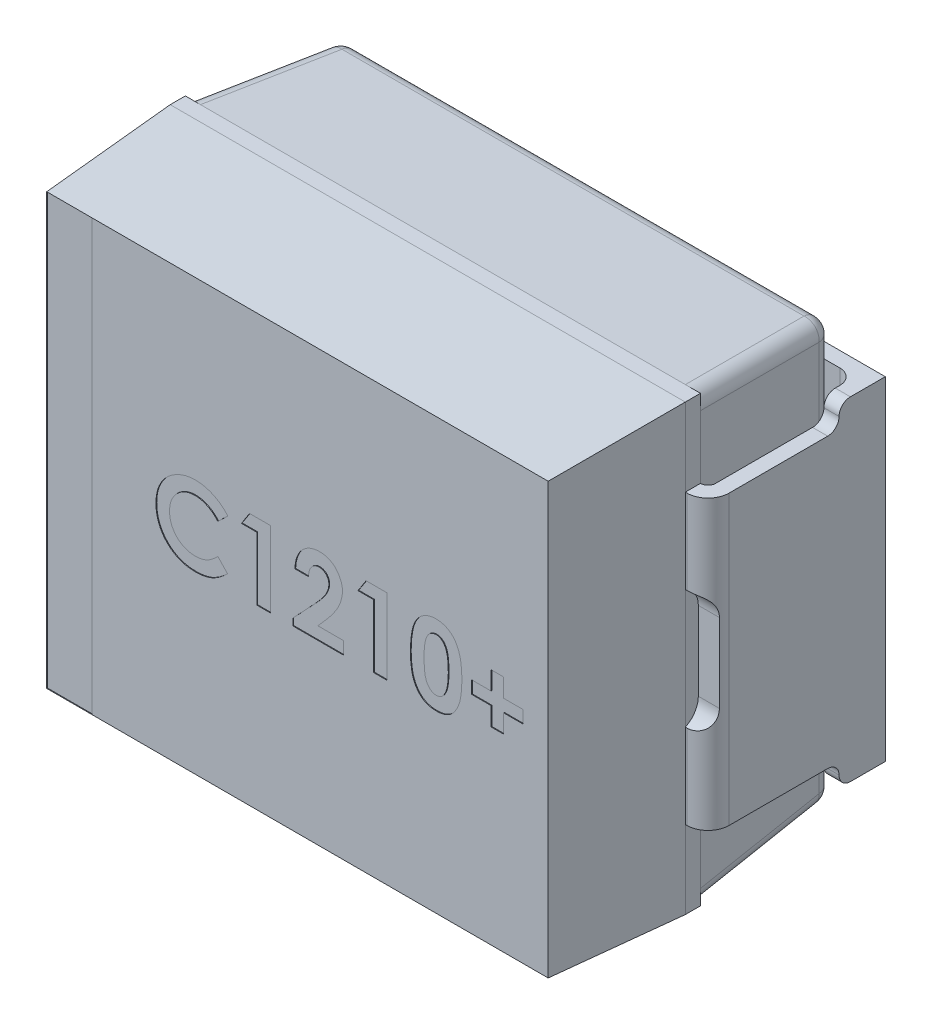
SolidWorks part; units mm, degrees
ref_plane "Front Plane" through (0, 0, 0) normal (0, 0, 1) x (1, 0, 0)
ref_plane "Top Plane" through (0, 0, 0) normal (0, 1, 0) x (1, 0, 0)
ref_plane "Right Plane" through (0, 0, 0) normal (1, 0, 0) x (0, 0, -1)
sketch "Sketch1" plane through (0, 0, 0) normal (0, 0, 1) x (1, 0, 0)
  line L1 (-1.7, -1.465) -> (-1.7, 1.465)
  line L2 (-1.7, -1.465) -> (1.7, -1.465)
  line L3 (1.7, -1.465) -> (1.7, 1.465)
  line L4 (-1.7, 1.465) -> (1.7, 1.465)
  dimension "D1" = 3.4
  dimension "D2" = 2.93
  dimension "D3" = 1.465
  dimension "D4" = 1.7
extrude "Boss-Extrude1" add sketch "Sketch1" along normal blind 0.95 from offset 0.12
ref_plane "Plane1" through (0, 0, 1.07) normal (0, 0, 1) x (1, 0, 0)
ref_plane "Plane2" through (0, 0, 1.17) normal (0, 0, 1) x (1, 0, 0)
sketch "Sketch2" plane through (0, 0, 1.07) normal (0, 0, 1) x (1, 0, 0)
  line L1 (-1.7, -1.465) -> (-1.7, 1.465)
  line L2 (-1.7, -1.465) -> (1.7, -1.465)
  line L3 (1.7, -1.465) -> (1.7, 1.465)
  line L4 (-1.7, 1.465) -> (1.7, 1.465)
  dimension "D1" = 1.7
  dimension "D2" = 2.93
  dimension "D3" = 1.465
  dimension "D4" = 3.4
sketch "Sketch3" plane through (0, 0, 1.17) normal (0, 0, 1) x (1, 0, 0)
  line L1 (-1.7, -1.465) -> (-1.7, 1.465)
  line L2 (-1.7, -1.465) -> (1.7, -1.465)
  line L3 (1.7, -1.465) -> (1.7, 1.465)
  line L4 (-1.7, 1.465) -> (1.7, 1.465)
  dimension "D1" = 1.465
  dimension "D2" = 2.93
  dimension "D3" = 1.7
  dimension "D4" = 3.4
chamfer "Chamfer3" distance 0.95 angle 5 4 edges at (0, -1.465, 0.12) (1.7, 0, 0.12) (0, 1.465, 0.12) (-1.7, 0, 0.12) first distance on face at (0, -1.465, 0.595) first distance on face at (1.7, 0, 0.595) first distance on face at (0, 1.465, 0.595) first distance on face at (-1.7, 0, 0.595)
fillet "Fillet4" radius 0.1 8 edges at (-1.6584, -1.4234, 0.595) (1.6584, -1.4234, 0.595) (1.6584, 1.4234, 0.595) (-1.6584, 1.4234, 0.595) (1.6169, 0, 0.12) (0, -1.3819, 0.12) (-1.6169, 0, 0.12) (0, 1.3819, 0.12)
extrude "Boss-Extrude2" add sketch "Sketch2" along normal blind 0.1
extrude "Boss-Extrude3" add sketch "Sketch3" along normal blind 0.86 draft 3
sketch "Sketch4" plane through (0, 0, 0) normal (0, 0, 1) x (1, 0, 0)
  line L1 (-0.7, -1.25) -> (-0.7, 1.25)
  line L2 (-0.7, -1.25) -> (0.7, -1.25)
  line L3 (0.7, -1.25) -> (0.7, 1.25)
  line L4 (-0.7, 1.25) -> (0.7, 1.25)
  dimension "D1" = 0.7
  dimension "D2" = 2.5
  dimension "D3" = 1.4
  dimension "D4" = 1.25
extrude "Boss-Extrude4" add sketch "Sketch4" along normal blind 0.1 from offset 0.02
fillet "Fillet5" radius 0.1 4 edges at (0, -1.25, 0.02) (0.7, 0, 0.02) (0, 1.25, 0.02) (-0.7, 0, 0.02)
sketch "Sketch6" plane through (0, 0, 0) normal (0, 1, 0) x (1, 0, 0)
  line L0 (-1.7, -1.17) -> (-1.7, -1.07)
  line L1 (-1.6116, -1.17) -> (1.6116, -1.17) construction
  line L2 (-1.6549, -2.03) -> (-1.7, -1.17) construction
  line L3 (-1.6116, -1.07) -> (1.6116, -1.07) construction
  line L4 (-1.7, -1.17) -> (-1.7, -1.07) construction
  line L5 (-1.7, -1.07) -> (-1.701, -1.07)
  line L6 (-1.75, -1.021) -> (-1.75, -0.2)
  line L7 (-1.65, -0.1) -> (-1.15, -0.1)
  line L8 (0, -0.02) -> (0, -2.03) construction
  line L9 (-1.15, -0.1) -> (-1.15, 0)
  line L10 (-1.15, 0) -> (-1.85, 0)
  line L11 (-1.85, 0) -> (-1.85, -1.03)
  line L12 (-1.71, -1.17) -> (-1.7, -1.17)
  line L13 (-0.6, -0.02) -> (0.6, -0.02) construction
  line L14 (1.6549, -2.03) -> (-1.6549, -2.03) construction
  line L15 (1.71, -1.17) -> (1.7, -1.17)
  line L16 (1.85, 0) -> (1.85, -1.03)
  line L17 (1.15, 0) -> (1.85, 0)
  line L18 (1.15, -0.1) -> (1.15, 0)
  line L19 (1.65, -0.1) -> (1.15, -0.1)
  line L20 (1.75, -1.021) -> (1.75, -0.2)
  line L21 (1.7, -1.07) -> (1.701, -1.07)
  line L22 (1.7, -1.17) -> (1.7, -1.07)
  arc A0 (-1.85, -1.03) -> (-1.71, -1.17) centre (-1.71, -1.03) ccw
  arc A1 (-1.701, -1.07) -> (-1.75, -1.021) centre (-1.701, -1.021) cw
  arc A2 (-1.75, -0.2) -> (-1.65, -0.1) centre (-1.65, -0.2) cw
  arc A3 (1.75, -0.2) -> (1.65, -0.1) centre (1.65, -0.2) ccw
  arc A4 (1.701, -1.07) -> (1.75, -1.021) centre (1.701, -1.021) ccw
  arc A5 (1.85, -1.03) -> (1.71, -1.17) centre (1.71, -1.03) cw
  point P15 (-1.85, -1.17)
  point P21 (-1.75, -1.07)
  point P24 (-1.75, -0.1)
  point P45 (1.75, -0.1)
  point P46 (1.75, -1.07)
  point P47 (1.85, -1.17)
  dimension "D6" = 0.14
  dimension "D7" = 0.049
  dimension "D8" = 0.1
  dimension "D1" = 0.97
  dimension "D2" = 0.15
  dimension "D3" = 0.1
  dimension "D4" = 0.1
  dimension "D5" = 0.7
extrude "Boss-Extrude5" add sketch "Sketch6" along normal mid plane 2.2
ref_plane "Plane3" through (-1.85, 0, 0) normal (-1, 0, 0) x (0, 0, 1)
sketch "Sketch7" plane through (-1.85, 0, 0) normal (-1, 0, 0) x (0, 0, 1)
  line L0 (0, 0) -> (2.03, 0) construction
  line L1 (2.03, 1.4199) -> (2.03, -1.4199) construction
  line L2 (1.17, 1.1) -> (1.17, -1.1) construction
  line L4 (1.17, 0.475) -> (0.559, 0.475)
  line L5 (1.17, 0.475) -> (1.17, -0.475)
  line L6 (1.17, -0.475) -> (0.559, -0.475)
  line L7 (0.459, 0.375) -> (0.459, -0.375)
  arc A0 (0.559, -0.475) -> (0.459, -0.375) centre (0.559, -0.375) cw
  arc A1 (0.559, 0.475) -> (0.459, 0.375) centre (0.559, 0.375) ccw
  point P16 (0.459, 0.475)
  dimension "D4" = 0.1
  dimension "D1" = 0.475
  dimension "D2" = 0.95
  dimension "D3" = 0.711
extrude "Cut-Extrude3" cut sketch "Sketch7" against normal blind 0.15
sketch "Sketch11" plane through (1.7, 0, -3.4788) normal (-1, 0, 0) x (0, 0, 1)
  line L0 (4.6488, -1.1) -> (3.7088, -1.1)
  line L1 (4.6488, -0.95) -> (4.6488, -1.1)
  line L2 (4.5088, 1.1) -> (3.4788, 1.1) construction
  line L3 (4.6488, 1.1) -> (4.6488, -1.1) construction
  line L4 (3.8588, -0.95) -> (4.6488, -0.95)
  line L14 (3.4788, 0) -> (4.6488, 0) construction
  line L16 (3.4788, 1.1) -> (3.4788, -1.1) construction
  line L18 (4.6477, 0.393) -> (4.6488, 0.3935)
  line L19 (4.5628, -0.2597) -> (4.5628, 0.2597)
  line L20 (4.6488, -0.3935) -> (4.6477, -0.393)
  line L21 (4.6488, 0.3935) -> (4.6488, -0.3935)
  line L22 (3.8588, 0.95) -> (4.6488, 0.95)
  line L23 (4.6488, 0.95) -> (4.6488, 1.1)
  line L24 (4.6488, 1.1) -> (3.7088, 1.1)
  arc A0 (3.7838, -1.025) -> (3.8588, -0.95) centre (3.8588, -1.025) cw
  arc A1 (3.7838, -1.025) -> (3.7088, -1.1) centre (3.7088, -1.025) cw
  arc A6 (4.5628, 0.2597) -> (4.6477, 0.393) centre (4.7098, 0.2597) cw
  arc A7 (4.6477, -0.393) -> (4.5628, -0.2597) centre (4.7098, -0.2597) cw
  arc A8 (3.7838, 1.025) -> (3.7088, 1.1) centre (3.7088, 1.025) ccw
  arc A9 (3.7838, 1.025) -> (3.8588, 0.95) centre (3.8588, 1.025) ccw
  dimension "D2" = 0.15
  dimension "D3" = 0.94
  dimension "D6" = 0.147
  dimension "D1" = 1.17
  dimension "D4" = 0.086
  dimension "D5" = 0.787
  dimension "D7" = 65
  dimension "D8" = 65
extrude "Cut-Extrude6" cut sketch "Sketch11" against normal blind 0.15
sketch "Sketch15" plane through (0, 0, 2.03) normal (0, 0, 1) x (1, 0, 0)
  line L0 (-1.061, -0.25) -> (1.6549, -0.25) construction
  line L1 (1.1165, 0) -> (-1.1165, 0) construction
  text T0 "<b>C1210+</b>" font "Century Gothic" height 0.5
  point P5 (0, 0)
  point P6 (-1.3574, -0.25)
  point P7 (-1.061, -0.25)
  dimension "D1" = 0.25
extrude "Cut-Extrude7" cut sketch "Sketch15" against normal blind 0.005
sketch "Sketch16" plane through (0, 0, 2.03) normal (0, 0, 1) x (1, 0, 0)
  line L0 (-1.6549, -1.4199) -> (1.6549, -1.4199) construction
  line L1 (-1.6549, 1.4199) -> (-1.3549, 1.4199)
  line L2 (-1.6549, 1.4199) -> (-1.6549, -1.4199)
  line L3 (-1.6549, -1.4199) -> (-1.3549, -1.4199)
  line L4 (-1.3549, 1.4199) -> (-1.3549, -1.4199)
  dimension "D1" = 0.3
extrude "Cut-Extrude8" cut sketch "Sketch16" against normal blind 0.005
